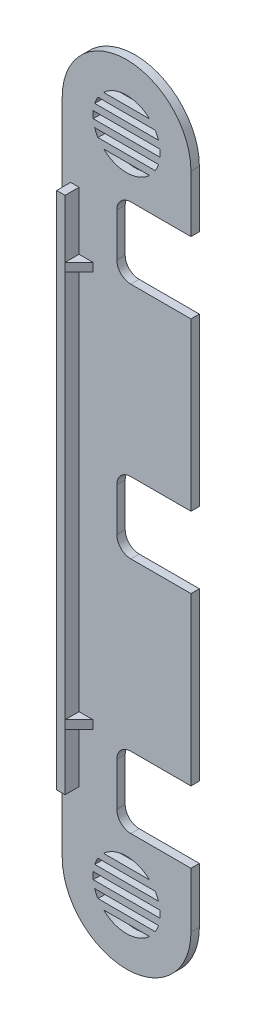
SolidWorks part; units mm, degrees
ref_plane "Front Plane" through (0, 0, 0) normal (0, 0, 1) x (1, 0, 0)
ref_plane "Top Plane" through (0, 0, 0) normal (0, 1, 0) x (1, 0, 0)
ref_plane "Right Plane" through (0, 0, 0) normal (1, 0, 0) x (0, 0, -1)
sketch "Sketch1" plane through (0, 0, 0) normal (0, 0, 1) x (1, 0, 0)
  line L0 (-23.5, 139.9624) -> (-23.5, 114.5)
  line L1 (-43, 160.25) -> (-43, -75.25)
  line L2 (3, 160.25) -> (3, 139.9624)
  line L4 (-23.5, -30.0376) -> (3, -30.0376)
  line L6 (-23.5, -55.5) -> (3, -55.5)
  line L8 (-23.5, 54.9624) -> (3, 54.9624)
  line L10 (-23.5, 29.5) -> (3, 29.5)
  line L12 (-23.5, 139.9624) -> (3, 139.9624)
  line L14 (-23.5, 114.5) -> (3, 114.5)
  line L16 (-23.5, 54.9624) -> (-23.5, 29.5)
  line L17 (-23.5, -30.0376) -> (-23.5, -55.5)
  line L24 (3, -55.5) -> (3, -75.25)
  line L25 (3, 29.5) -> (3, -30.0376)
  line L26 (3, 114.5) -> (3, 54.9624)
  arc A2 (3, 160.25) -> (-43, 160.25) centre (-20, 160.25) ccw
  arc A3 (-43, -75.25) -> (3, -75.25) centre (-20, -75.25) ccw
extrude "Boss-Extrude1" add sketch "Sketch1" along normal blind 3
fillet "Fillet1" radius 5 6 edges at (-23.5, 139.9624, 1.5) (-23.5, 114.5, 1.5) (-23.5, 54.9624, 1.5) (-23.5, 29.5, 1.5) (-23.5, -55.5, 1.5) (-23.5, -30.0376, 1.5)
sketch "Sketch2" plane through (0, 0, 3) normal (0, 0, 1) x (1, 0, 0)
  line L0 (-20, 183.25) -> (-20, -98.25) construction
  line L1 (-20, 42.5) -> (-43, 42.5) construction
  line L2 (-43, 160.25) -> (-43, -75.25) construction
  line L3 (3, 84.7312) -> (-20, 84.7312) construction
  line L4 (3, 54.9624) -> (3, 114.5) construction
  line L5 (-32, 160.25) -> (-8, 160.25) construction
  line L6 (-31.9347, 161.5) -> (-8.0653, 161.5)
  line L7 (-31.399, 164) -> (-8.601, 164)
  line L8 (-30.2439, 166.5) -> (-9.7561, 166.5)
  line L9 (-28.212, 169) -> (-11.788, 169)
  line L10 (-31.9347, 159) -> (-8.0653, 159)
  line L11 (-28.212, 151.5) -> (-11.788, 151.5)
  line L12 (-30.2439, 154) -> (-9.7561, 154)
  line L13 (-31.399, 156.5) -> (-8.601, 156.5)
  line L14 (-32, -75.25) -> (-8, -75.25) construction
  line L15 (-31.399, -71.5) -> (-8.601, -71.5)
  line L16 (-30.2439, -69) -> (-9.7561, -69)
  line L17 (-28.212, -66.5) -> (-11.788, -66.5)
  line L18 (-31.9347, -74) -> (-8.0653, -74)
  line L19 (-28.212, -84) -> (-11.788, -84)
  line L20 (-30.2439, -81.5) -> (-9.7561, -81.5)
  line L21 (-31.399, -79) -> (-8.601, -79)
  line L22 (-31.9347, -76.5) -> (-8.0653, -76.5)
  line L47 (3, 0.2688) -> (-20, 0.2688) construction
  arc A0 (3, 160.25) -> (-43, 160.25) centre (-20, 160.25) ccw construction
  arc A1 (-43, -75.25) -> (3, -75.25) centre (-20, -75.25) ccw construction
  arc A2 (-30.2439, 166.5) -> (-31.399, 164) centre (-20, 160.25) ccw
  arc A3 (-11.788, 169) -> (-28.212, 169) centre (-20, 160.25) ccw
  arc A4 (-8.601, 164) -> (-9.7561, 166.5) centre (-20, 160.25) ccw
  arc A5 (-31.9347, 161.5) -> (-31.9347, 159) centre (-20, 160.25) ccw
  arc A6 (-31.399, 156.5) -> (-30.2439, 154) centre (-20, 160.25) ccw
  arc A7 (-8.0653, 159) -> (-8.0653, 161.5) centre (-20, 160.25) ccw
  arc A8 (-9.7561, 154) -> (-8.601, 156.5) centre (-20, 160.25) ccw
  arc A9 (-28.212, 151.5) -> (-11.788, 151.5) centre (-20, 160.25) ccw
  arc A10 (-28.212, -66.5) -> (-11.788, -66.5) centre (-20, -75.25) cw
  arc A11 (-9.7561, -69) -> (-8.601, -71.5) centre (-20, -75.25) cw
  arc A12 (-8.0653, -74) -> (-8.0653, -76.5) centre (-20, -75.25) cw
  arc A13 (-31.399, -71.5) -> (-30.2439, -69) centre (-20, -75.25) cw
  arc A14 (-31.9347, -76.5) -> (-31.9347, -74) centre (-20, -75.25) cw
  arc A15 (-8.601, -79) -> (-9.7561, -81.5) centre (-20, -75.25) cw
  arc A16 (-11.788, -84) -> (-28.212, -84) centre (-20, -75.25) cw
  arc A17 (-30.2439, -81.5) -> (-31.399, -79) centre (-20, -75.25) cw
  dimension "D1" = 1.25
  dimension "D2" = 2.5
  dimension "D3" = 2.5
  dimension "D4" = 2.5
extrude "Cut-Extrude1" cut sketch "Sketch2" against normal up to surface (3 mm away) up to face at (-14.5551, 42.2801, 0)
sketch "Sketch3" plane through (0, 0, 3) normal (0, 0, 1) x (1, 0, 0)
  line L1 (-40, -50.25) -> (-37, -50.25)
  line L2 (-40, -50.25) -> (-40, 135.25)
  line L3 (-40, 135.25) -> (-37, 135.25)
  line L4 (-37, -50.25) -> (-37, 135.25)
  line L6 (-43, 148.0073) -> (-43, -63.0073) construction
  arc A0 (3, 160.25) -> (-43, 160.25) centre (-20, 160.25) ccw construction
  arc A1 (-43, -75.25) -> (-3.6462, -91.4226) centre (-20, -75.25) ccw construction
  point P4 (0, 0)
  dimension "D3" = 25
  dimension "D1" = 3
  dimension "D2" = 25
  dimension "D4" = 3
extrude "Boss-Extrude2" add sketch "Sketch3" along normal blind 5
sketch "Sketch4" plane through (0, -30.0376, 0) normal (0, -1, 0) x (1, 0, 0)
  line L0 (-37, 8) -> (-37, 3) construction
  line L1 (-37, 8) -> (-37, 3)
  line L2 (-37, 3) -> (-32, 3)
  line L3 (3, 3) -> (-43, 3) construction
  line L4 (-32, 3) -> (-37, 8)
  dimension "D1" = 45
extrude "Boss-Extrude3" add sketch "Sketch4" against normal blind 3
sketch "Sketch5" plane through (0, 114.5, 0) normal (0, 1, 0) x (1, 0, 0)
  line L3 (-37, -8) -> (-32, -3)
  line L4 (-37, -3) -> (-37, -8)
  line L5 (-32, -3) -> (-37, -3)
  line L6 (-37, -8) -> (-32, -3)
  line L7 (-37, -3) -> (-37, -8)
  line L8 (-32, -3) -> (-37, -3)
  dimension "D1" = 0
extrude "Boss-Extrude4" add sketch "Sketch5" against normal blind 3
